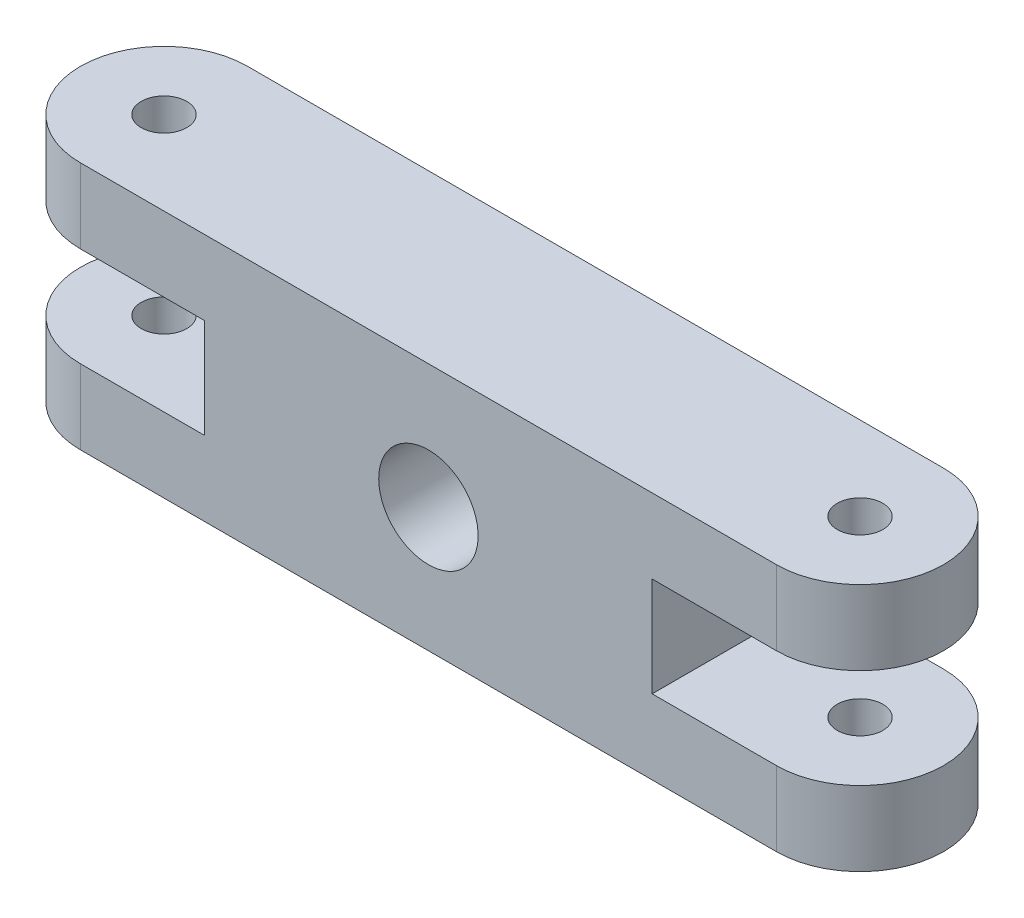
SolidWorks part; units mm, degrees
ref_plane "Front Plane" through (0, 0, 0) normal (0, 0, 1) x (1, 0, 0)
ref_plane "Top Plane" through (0, 0, 0) normal (0, 1, 0) x (1, 0, 0)
ref_plane "Right Plane" through (0, 0, 0) normal (1, 0, 0) x (0, 0, -1)
sketch "Sketch1" plane through (0, 0, 0) normal (0, 1, 0) x (1, 0, 0)
  line L0 (0, 0) -> (-42, 0)
  line L1 (-42, -10.0853) -> (42, -10.0853)
  line L2 (-42, -10.0853) -> (-42, 10.0853)
  line L3 (-42, 10.0853) -> (42, 10.0853)
  line L4 (42, -10.0853) -> (42, 10.0853)
  line L5 (-42, -10.0853) -> (42, 10.0853) construction
  line L6 (-42, 10.0853) -> (42, -10.0853) construction
  circle A0 centre (-42, 0) radius 10.0853
  circle A1 centre (42, 0) radius 10.0853
  circle A2 centre (-42, 0) radius 2.75
  circle A3 centre (42, 0) radius 2.75
  point P0 (0, 0)
  point P14 (-41.1196, 0)
extrude "Boss-Extrude1" add sketch "Sketch1" along normal blind 30 contours A2 L2 A0 | A2 L0 A0 L2 | A2 L2 A0 L0 | A1 L3 A0 L1 | A3 L4 A1 | A3 L4 A1 region at (-37.4696, 0, 4.5304) region at (-37.4696, 0, -4.5304) region at (-34.2577, 0, -7.7423) region at (-46.5304, 0, 0) region at (46.5304, 0, 0) region at (37.4696, 0, 0)
sketch "Sketch4" plane through (0, 0, -10.0853) normal (0, 0, -1) x (-1, 0, 0)
  line L0 (42, 15) -> (42, 9)
  line L1 (42, 30) -> (42, 0) construction
  line L2 (42, 9) -> (27, 9)
  line L3 (27, 9) -> (27, 21)
  line L4 (27, 21) -> (67.855, 21)
  line L5 (67.855, 21) -> (67.855, 9)
  line L6 (67.855, 9) -> (42, 9)
  line L7 (0, 0) -> (0, 12)
  line L8 (42, 0) -> (-42, 0) construction
  line L9 (-67.855, 9) -> (-42, 9)
  line L10 (-67.855, 21) -> (-67.855, 9)
  line L11 (-27, 21) -> (-67.855, 21)
  line L12 (-27, 9) -> (-27, 21)
  line L13 (-42, 9) -> (-27, 9)
  line L14 (-42, 15) -> (-42, 9)
  circle A0 centre (0, 15) radius 6
  line M3 (42, 0) -> (42, 30)
  line M5 (-42, 30) -> (-42, 0)
extrude "Cut-Extrude1" cut sketch "Sketch4" against normal blind 27 contours L6 L5 L4 M3 | L4 L3 L2 M3 | L13 L12 L11 M5 | L11 L10 L9 M5 region at (-54.9275, 15, -10.0853) region at (-34.5, 15, -10.0853) region at (54.9275, 15, -10.0853) region at (34.5, 15, -10.0853)
extrude "Cut-Extrude2" cut sketch "Sketch4<3>" against normal blind 27 contours A0 region at (0, 15, -10.0853)
sketch "Sketch4<3>" plane through (0, 0, -10.0853) normal (0, 0, -1) x (-1, 0, 0) same geometry as "Sketch4"
